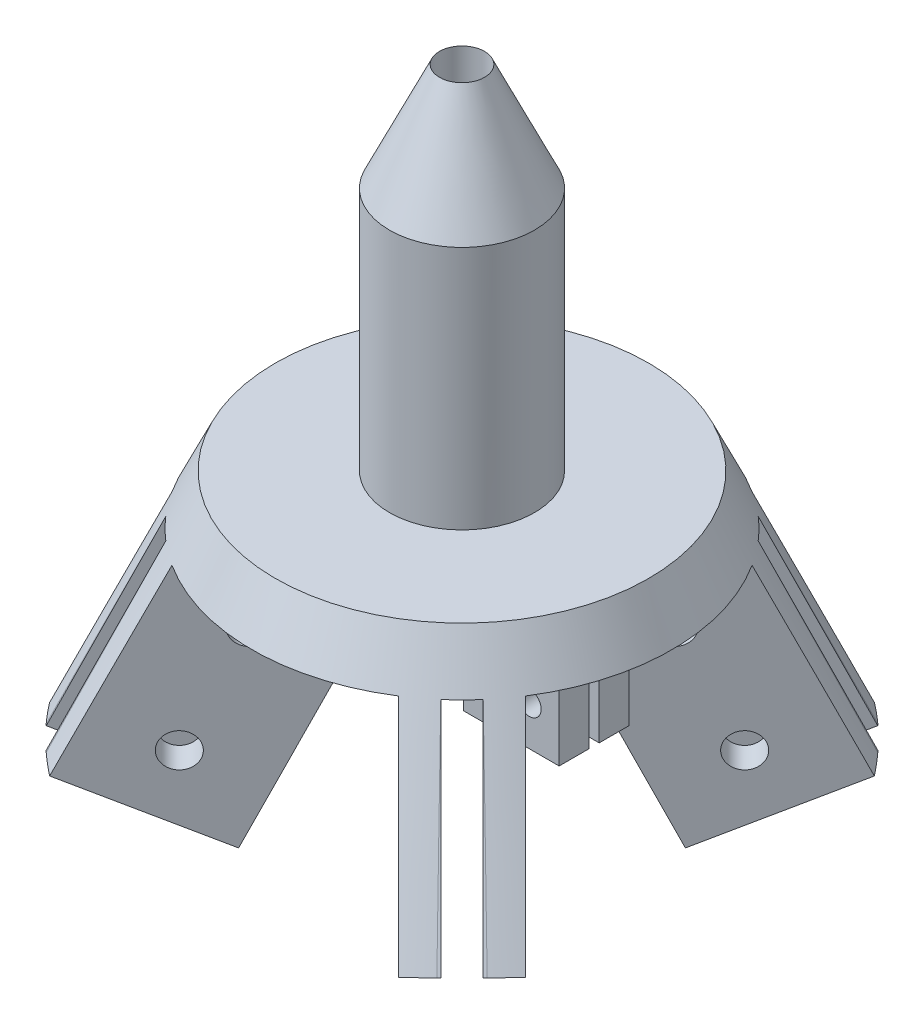
SolidWorks part; units mm, degrees
note: '?' marks a value the reader was unsure of.
ref_plane "Front Plane" through (0, 0, 0) normal (0, 0, 1) x (1, 0, 0)
ref_plane "Top Plane" through (0, 0, 0) normal (0, 1, 0) x (1, 0, 0)
ref_plane "Right Plane" through (0, 0, 0) normal (1, 0, 0) x (0, 0, -1)
ref_axis "Axis1" through (0, 55, 0) along (0, -1, 0)?
sketch "Sketch3" plane through (0, 0, 0) normal (0, 0, 1) x (1, 0, 0)
  line L0 (0, 21.4294) -> (0, -11.4772) construction
  line L1 (0, 55) -> (0, -55) construction
  line L2 (2.25, 0) -> (2.25, 40.1749)
  line L3 (2.25, 40.1749) -> (7.25, 29.4523)
  line L4 (20.9838, 0) -> (2.25, 0)
  line L5 (7.25, 29.4523) -> (7.25, 5)
  line L6 (7.25, 5) -> (18.6523, 5)
  line L7 (18.6523, 5) -> (20.9838, 0)
  line L8 (2.25, 40.1749) -> (0, 45) construction
  dimension "D1" = 4.5
  dimension "D3" = 25
  dimension "D4" = 5
  dimension "D5" = 5
  dimension "D6" = 45
revolve "Revolve1" add sketch "Sketch3" angle 360 about L0
ref_plane "Plane1" through (0, 0, 0.5) normal (0, 0, 1) x (1, 0, 0)
sketch "Sketch4" plane through (0, 0, 0.5) normal (0, 0, 1) x (1, 0, 0)
  line L0 (-20.9838, 0) -> (20.9838, 0) construction
  line L1 (3.6708, 0) -> (13.21, 0)
  line L2 (3.6708, 0) -> (3.6708, -12.2)
  line L3 (3.6708, -12.2) -> (13.21, -12.2)
  line L4 (13.21, 0) -> (13.21, -12.2)
  line L5 (11.21, -12.2) -> (3.1708, -12.2) construction
  line L6 (3.1708, -12.2) -> (3.1708, -4.2) construction
  line L7 (13.21, -10.2) -> (13.21, -6.2) construction
  point P6 (0, 0)
  dimension "D1" = 0.5
extrude "Boss-Extrude1" add sketch "Sketch4" along normal blind 3
mirror "Mirror1" about plane through (0, 0, 0) normal (0, 0, 1) of "Boss-Extrude1"
ref_plane "Plane3" through (0, 0, 0) normal (-0.7071, 0, 0.7071) x (0, -1, 0)
ref_plane "Plane2" through (-1.0607, 0, 1.0607) normal (-0.7071, 0, 0.7071) x (0, -1, 0)
sketch "Sketch9" plane through (-1.0607, 0, 1.0607) normal (-0.7071, 0, 0.7071) x (0, -1, 0)
  line L1 (0, 20.9302) -> (18.1262, 29.3825)
  line L2 (18.1262, 29.3825) -> (24.4654, 15.7879)
  line L3 (24.4654, 15.7879) -> (0, 4.3795)
  line L4 (0, 4.3795) -> (0, 20.9302)
  line L7 (-55, 0) -> (55, 0) construction
  dimension "D1" = 15
  dimension "D2" = 25
  dimension "D3" = 20
extrude "Boss-Extrude2" add sketch "Sketch9" along normal blind 3
sketch "Sketch10" plane through (0, 0, 0) normal (0.7071, 0, -0.7071) x (-0.7071, 0, -0.7071)
  line L0 (-2.25, 40.1749) -> (-32.3923, -24.4654)
  line L1 (-32.3923, -24.4654) -> (-32.3923, 40.1749)
  line L2 (-32.3923, 40.1749) -> (-2.25, 40.1749)
  line L4 (-29.3825, -18.1262) -> (-20.9302, 0) construction
revolve "Cut-Revolve1" cut sketch "Sketch10" angle 360 about axis through (0, 55, 0) along (0, -1, 0)
mirror "Mirror2" about plane through (0, 0, 0) normal (-0.7071, 0, 0.7071) of "Boss-Extrude2", "Cut-Revolve1"
pattern_circular "CirPattern2" count 4 over 360 about axis through (0, 0, 0) along (0, 1, 0) of "Boss-Extrude2", "Cut-Revolve1", "Mirror2"
sketch "Sketch8" plane through (0, 0, 3.5) normal (0, 0, 1) x (1, 0, 0)
  circle A0 centre (10.21, -8.2) radius 1.2
  circle A1 centre (10.21, -8.2) radius 1.2 construction
extrude "Cut-Extrude1" cut sketch "Sketch8" against normal up to surface and the other way through all up to face at (7.5976, -3.7393, 0.5)
hole_wizard "Tap Drill for M2x0.4 Tap1" positions "Sketch12" profile "Sketch13" hole size "M2x0.4" standard "ANSI Metric"
sketch "Sketch12" plane through (0, 0, -0.5) normal (0, 0, 1) x (1, 0, 0)
  point P0 (10.21, -8.2)
sketch "Sketch13" plane through (10.21, -8.2, -0.5) normal (1, 0, 0) x (0, -1, 0)
  line L0 (0, 0) -> (0, 3)
  line L1 (0, 3) -> (0.8, 3)
  line L2 (0.8, 3) -> (0.8, 0)
  line L5 (0.8, 0) -> (0, 0)
  line L11 (0, -6.35) -> (0, 107.95) construction
  dimension "Thru Hole Dia." = 1.6
  dimension "Thru Hole Depth" = 3
hole_wizard "M3 Clearance Hole1" positions "Sketch14" profile "Sketch15" hole size "M3" standard "ANSI Metric"
sketch "Sketch14" plane through (-3.182, 0, 3.182) normal (-0.7071, 0, 0.7071) x (0.7071, 0, 0.7071)
  line L0 (22.4654, -21.3517) -> (17.4872, -10.6758) construction
  line L1 (15.7879, -24.4654) -> (29.1429, -18.2379) construction
  line L2 (17.4872, -10.6758) -> (12.509, 0) construction
  line L5 (20.4957, 0) -> (4.5, 0) construction
  point P12 (19.9763, -16.0137)
  point P14 (14.9981, -5.3379)
sketch "Sketch15" plane through (7.4233, -5.3379, 13.7872) normal (0, 1, 0) x (0.7071, 0, 0.7071)
  line L0 (0, 0) -> (0, 3)
  line L1 (0, 3) -> (1.7, 3)
  line L2 (1.7, 3) -> (1.7, 0)
  line L5 (1.7, 0) -> (0, 0)
  line L11 (0, -6.35) -> (0, 107.95) construction
  dimension "Thru Hole Dia." = 3.4
  dimension "Thru Hole Depth" = 3
hole_wizard "M3 Clearance Hole2" positions "Sketch16" profile "Sketch17" hole size "M3" standard "ANSI Metric" end condition up to next
sketch "Sketch16" plane through (1.0607, 0, -1.0607) normal (-0.7071, 0, 0.7071) x (0.7071, 0, 0.7071)
  circle A0 centre (14.9981, -5.3379) radius 1.7
  circle A1 centre (19.9763, -16.0137) radius 1.7
  circle A2 centre (19.9763, -16.0137) radius 1.7 construction
  circle A3 centre (14.9981, -5.3379) radius 1.7 construction
  point P0 (19.9763, -16.0137)
  point P3 (14.9981, -5.3379)
sketch "Sketch17" plane through (15.186, -16.0137, 13.0647) normal (0, 1, 0) x (0.7071, 0, 0.7071)
  line L0 (0, 0) -> (0, 3)
  line L1 (0, 3) -> (1.7, 3)
  line L2 (1.7, 3) -> (1.7, 0)
  line L5 (1.7, 0) -> (0, 0)
  line L11 (0, -6.35) -> (0, 107.95) construction
  dimension "Thru Hole Dia." = 3.4
  dimension "Thru Hole Depth" = 3
pattern_circular "CirPattern3" count 4 over 360 about axis through (0, 55, 0) along (0, -1, 0) of "M3 Clearance Hole1", "M3 Clearance Hole2"
